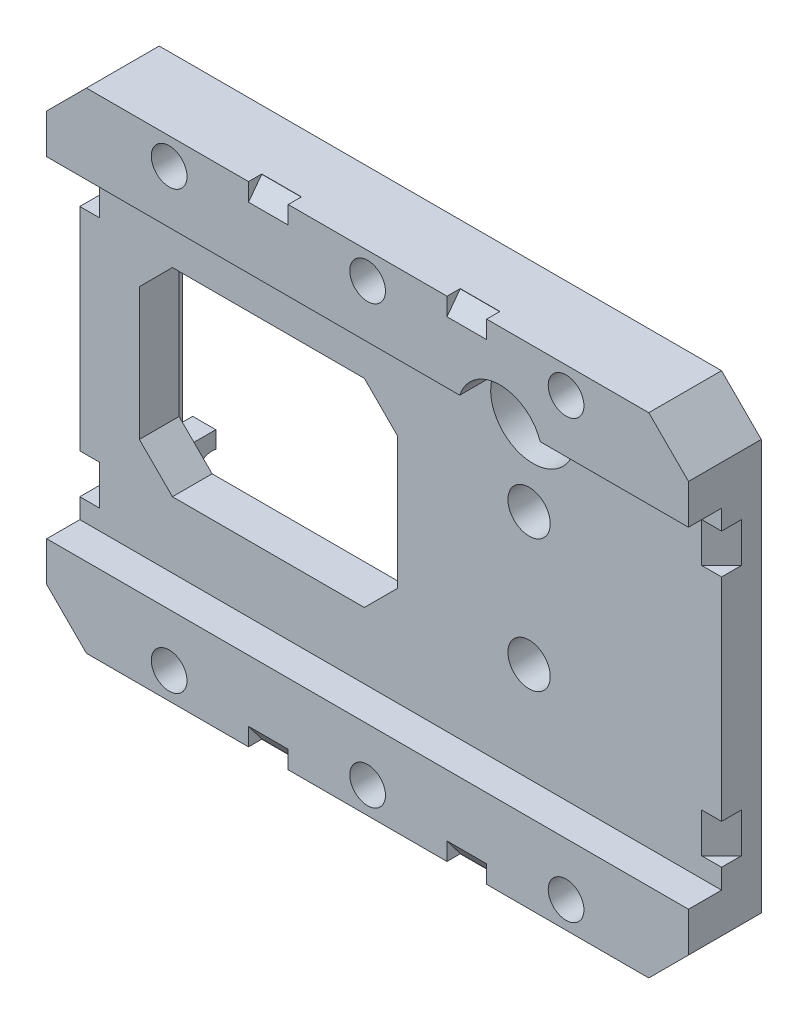
SolidWorks part; units mm, degrees
ref_plane "前视基准面" through (0, 0, 0) normal (0, 0, 1) x (1, 0, 0)
ref_plane "上视基准面" through (0, 0, 0) normal (0, 1, 0) x (1, 0, 0)
ref_plane "右视基准面" through (0, 0, 0) normal (1, 0, 0) x (0, 0, -1)
ref_plane "基准面4" through (0, 0, 5.028) normal (0, 0, -1) x (-1, 0, 0)
sketch "草图1" plane through (0, 0, 5.028) normal (0, 0, -1) x (-1, 0, 0)
  line L0 (-24.25, 18.5) -> (-24.25, -18.5)
  line L1 (-24.25, -18.5) -> (24.25, -18.5)
  line L2 (24.25, -18.5) -> (24.25, 18.5)
  line L3 (24.25, 18.5) -> (-24.25, 18.5)
  line L4 (-24.25, 0) -> (24.25, 0) construction
  line L5 (0, 18.5) -> (0, -18.5) construction
  point P8 (0, 0)
  dimension "D1" = 48.5
  dimension "D2" = 37
extrude "凸台-拉伸1" add sketch "草图1" against normal blind 7.5
sketch "草图2" plane through (24.25, 0, 0) normal (1, 0, 0) x (0, 0, -1)
  line L0 (-12.528, 12.5) -> (-12.528, -12.5)
  line L1 (-12.528, -12.5) -> (-8.028, -12.5)
  line L2 (-8.028, -12.5) -> (-8.028, 12.5)
  line L3 (-8.028, 12.5) -> (-12.528, 12.5)
extrude "切除-拉伸1" cut sketch "草图2" against normal through all
sketch "草图3" plane through (0, 0, 5.028) normal (0, 0, -1) x (-1, 0, 0)
  line L0 (21.75, 13.75) -> (21.75, -13.75)
  line L1 (21.75, -13.75) -> (-19.25, -13.75)
  line L2 (-19.25, -13.75) -> (-19.25, 13.75)
  line L3 (-19.25, 13.75) -> (21.75, 13.75)
  line L4 (-19.25, 0) -> (21.75, 0) construction
  line L5 (24.25, -18.5) -> (24.25, 18.5) construction
  line L6 (-24.25, 18.5) -> (-24.25, -18.5) construction
  point P4 (0, 0)
  point P8 (0, 0)
  point P9 (0, 0)
  dimension "D1" = 27.5
  dimension "D2" = 2.5
  dimension "D3" = 5
extrude "凸台-拉伸2" add sketch "草图3" along normal blind 3.028
sketch "草图4" plane through (0, 0, 2) normal (0, 0, -1) x (-1, 0, 0)
  line L0 (-18.25, -12.5) -> (20, -12.5)
  line L1 (20, -12.5) -> (20, 12.5)
  line L2 (20, 12.5) -> (-18.25, 12.5)
  line L3 (-18.25, 12.5) -> (-18.25, -12.5)
  line L5 (21.75, -13.75) -> (21.75, 13.75) construction
  line L6 (-19.25, 13.75) -> (-19.25, -13.75) construction
  line L7 (-19.25, -13.75) -> (21.75, -13.75) construction
  point P8 (0, 0)
  dimension "D1" = 1
  dimension "D2" = 1.25
  dimension "D3" = 1.75
extrude "切除-拉伸2" cut sketch "草图4" against normal blind 3.028
sketch "草图5" plane through (18.25, 0, 0) normal (-1, 0, 0) x (0, 0, 1)
  line L0 (2, 7.0344) -> (2, -7.0344)
  arc A0 (2, -7.0344) -> (2, 7.0344) centre (-7.722, 0) ccw
extrude "切除-拉伸3" cut sketch "草图5" against normal through all
sketch "草图6" plane through (-21.75, 0, 0) normal (-1, 0, 0) x (0, 0, 1)
  line L0 (2, 7.0344) -> (2, -7.0344)
  arc A0 (2, -7.0344) -> (2, 7.0344) centre (-7.722, 0) ccw
extrude "切除-拉伸4" cut sketch "草图6" against normal through all
sketch "草图7" plane through (0, 0, 8.028) normal (0, 0, 1) x (1, 0, 0)
  line L0 (-7.9784, 7.0292) -> (-13.0216, 7.0292)
  line L1 (-13.0216, -7.0292) -> (-7.9784, -7.0292)
  arc A0 (-1.5, 0) -> (-7.9784, 7.0292) centre (-7.9784, 0.5292) ccw
  arc A1 (-13.0216, 7.0292) -> (-19.5, 0) centre (-13.0216, 0.5292) ccw
  arc A2 (-19.5, 0) -> (-13.0216, -7.0292) centre (-13.0216, -0.5292) ccw
  arc A3 (-7.9784, -7.0292) -> (-1.5, 0) centre (-7.9784, -0.5292) ccw
  dimension "D1" = 19.5
  dimension "D2" = 18
extrude "切除-拉伸5" cut sketch "草图7" against normal through all
ref_plane "基准面5" through (0, 11.5, 0) normal (0, 1, 0) x (1, 0, 0)
sketch "草图8" plane through (0, 11.5, 0) normal (0, 1, 0) x (1, 0, 0)
  line L0 (13, -2.1) -> (10, -2.1)
  line L1 (10, -2.1) -> (10, -12.528)
  line L2 (10, -12.528) -> (13, -12.528)
  line L3 (13, -12.528) -> (13, -2.1)
  line L4 (10, -2.1) -> (10, -12.528) construction
hole_wizard "Ø2.5 (2.5) 直径孔1" positions "草图10" profile "草图9" hole size "Ø2.5" standard "ANSI Metric"
sketch "草图10" plane through (-21.75, 0, 0) normal (-1, 0, 0) x (0, 0, 1)
  point P0 (2.278, 10)
sketch "草图9" plane through (-21.75, 10, 2.278) normal (0, 1, 0) x (0, 0, 1)
  line L0 (0, 0) -> (0, 1.75)
  line L1 (0, 1.75) -> (1.25, 1.75)
  line L2 (1.25, 1.75) -> (1.25, 0)
  line L5 (1.25, 0) -> (0, 0)
  line L11 (0, -6.35) -> (0, 107.95) construction
  dimension "通孔孔直径" = 2.5
  dimension "通孔孔深度" = 1.75
hole_wizard "Ø2.5 (2.5) 直径孔2" positions "草图12" profile "草图11" hole size "Ø2.5" standard "ANSI Metric"
sketch "草图12" plane through (18.25, 0, 0) normal (-1, 0, 0) x (0, 0, 1)
  point P0 (2.278, -10)
  point P1 (2.278, 10)
sketch "草图11" plane through (18.25, -10, 2.278) normal (0, 1, 0) x (0, 0, 1)
  line L0 (0, 0) -> (0, 6)
  line L1 (0, 6) -> (1.25, 6)
  line L2 (1.25, 6) -> (1.25, 0)
  line L5 (1.25, 0) -> (0, 0)
  line L11 (0, -6.35) -> (0, 107.95) construction
  dimension "通孔孔直径" = 2.5
  dimension "通孔孔深度" = 6
hole_wizard "Ø2.5 (2.5) 直径孔3" positions "草图14" profile "草图13" hole size "Ø2.5" standard "ANSI Metric"
sketch "草图14" plane through (-20, 0, 0) normal (1, 0, 0) x (0, 0, -1)
  point P0 (-2.278, -10)
sketch "草图13" plane through (-20, -10, 2.278) normal (0, 1, 0) x (0, 0, -1)
  line L0 (0, 0) -> (0, 4.25)
  line L1 (0, 4.25) -> (1.25, 4.25)
  line L2 (1.25, 4.25) -> (1.25, 0)
  line L5 (1.25, 0) -> (0, 0)
  line L11 (0, -6.35) -> (0, 107.95) construction
  dimension "通孔孔直径" = 2.5
  dimension "通孔孔深度" = 4.25
hole_wizard "Ø2.7 (2.7) 直径孔1" positions "草图16" profile "草图15" hole size "Ø2.7" standard "ANSI Metric" end condition through all
sketch "草图16" plane through (0, 0, 12.528) normal (0, 0, 1) x (1, 0, 0)
  point P0 (0, -16.5)
  point P1 (-15, -16.5)
  point P2 (15, -16.5)
  point P3 (0, 16.5)
  point P4 (-15, 16.5)
  point P5 (15, 16.5)
sketch "草图15" plane through (0, -16.5, 12.528) normal (1, 0, 0) x (0, -1, 0)
  line L0 (0, 0) -> (0, 10.528)
  line L1 (0, 10.528) -> (1.35, 10.528)
  line L2 (1.35, 10.528) -> (1.35, 0)
  line L5 (1.35, 0) -> (0, 0)
  line L11 (0, -6.35) -> (0, 107.95) construction
  dimension "通孔孔直径" = 2.7
  dimension "通孔孔深度" = 10.528
chamfer "倒角1" distance 3 angle 45 4 edges at (24.25, -18.5, 8.778) (24.25, 18.5, 8.778) (-24.25, 18.5, 8.778) (-24.25, -18.5, 8.778)
sketch "草图17" plane through (0, 0, 12.528) normal (0, 0, 1) x (1, 0, 0)
  line L0 (-15, -16.5) -> (0, -16.5) construction
  line L1 (-9, -14.5) -> (-9, -18.5)
  line L2 (-9, -14.5) -> (-6, -14.5)
  line L3 (-9, -18.5) -> (-6, -18.5)
  line L4 (-6, -14.5) -> (-6, -18.5)
  line L5 (-9, -14.5) -> (-6, -18.5) construction
  line L6 (-9, -18.5) -> (-6, -14.5) construction
  line L7 (21.25, -18.5) -> (-21.25, -18.5) construction
  line L8 (0, -5.7904) -> (0, 5.7904) construction
  line L9 (9, -18.5) -> (6, -14.5) construction
  line L10 (9, -14.5) -> (6, -18.5) construction
  line L11 (6, -14.5) -> (6, -18.5)
  line L12 (9, -18.5) -> (6, -18.5)
  line L13 (9, -14.5) -> (6, -14.5)
  line L14 (9, -14.5) -> (9, -18.5)
  line L15 (5.7904, 0) -> (-5.7904, 0) construction
  line L16 (9, 14.5) -> (6, 18.5) construction
  line L17 (9, 18.5) -> (6, 14.5) construction
  line L18 (-9, 18.5) -> (-6, 14.5) construction
  line L19 (-9, 14.5) -> (-6, 18.5) construction
  line L20 (9, 14.5) -> (9, 18.5)
  line L21 (9, 14.5) -> (6, 14.5)
  line L22 (9, 18.5) -> (6, 18.5)
  line L23 (6, 14.5) -> (6, 18.5)
  line L24 (-6, 14.5) -> (-6, 18.5)
  line L25 (-9, 18.5) -> (-6, 18.5)
  line L26 (-9, 14.5) -> (-6, 14.5)
  line L27 (-9, 14.5) -> (-9, 18.5)
  point P4 (-7.5, -16.5)
  point P6 (-7.5, -16.5)
  point P18 (7.5, -16.5)
  point P29 (7.5, 16.5)
  point P30 (-7.5, 16.5)
  dimension "D1" = 3
extrude "切除-拉伸8" cut sketch "草图17" against normal blind 3
chamfer "倒角2" distance 3 angle 53 4 edges at (7.5, -14.5, 9.528) (-7.5, -14.5, 9.528) (-7.5, 14.5, 9.528) (7.5, 14.5, 9.528) first distance on face at (7.5, -14.5, 11.028) first distance on face at (-7.5, -14.5, 11.028) first distance on face at (-7.5, 14.5, 11.028) first distance on face at (7.5, 14.5, 11.028)
sketch "草图19" plane through (0, 0, 8.028) normal (0, 0, 1) x (1, 0, 0)
  line L0 (-24.25, -12.5) -> (-24.25, 12.5) construction
  line L1 (-24.25, -11) -> (-22.25, -11)
  line L2 (-24.25, -11) -> (-24.25, -8)
  line L3 (-24.25, -8) -> (-22.25, -8)
  line L4 (-22.25, -11) -> (-22.25, -8)
  line L6 (5.7904, 0) -> (-5.7904, 0) construction
  line L7 (-22.25, 11) -> (-22.25, 8)
  line L8 (-24.25, 8) -> (-22.25, 8)
  line L9 (-24.25, 11) -> (-24.25, 8)
  line L10 (-24.25, 11) -> (-22.25, 11)
  line L11 (-24.25, -14) -> (24.25, -14) construction
  line L12 (-24.25, -15.5) -> (-24.25, -12.5) construction
  line L13 (24.25, -12.5) -> (24.25, -15.5) construction
  line L14 (0, -14) -> (0, 21.3882) construction
  line L15 (24.25, 11) -> (22.25, 11)
  line L16 (24.25, 11) -> (24.25, 8)
  line L17 (24.25, 8) -> (22.25, 8)
  line L18 (22.25, 11) -> (22.25, 8)
  line L19 (22.25, -11) -> (22.25, -8)
  line L20 (24.25, -8) -> (22.25, -8)
  line L21 (24.25, -11) -> (24.25, -8)
  line L22 (24.25, -11) -> (22.25, -11)
  dimension "D1" = 3
  dimension "D2" = 2
  dimension "D3" = 8
extrude "切除-拉伸9" cut sketch "草图19" against normal blind 1.5
chamfer "倒角3" distance 2 angle 45 4 edges at (22.25, 9.5, 6.528) (22.25, -9.5, 6.528) (-22.25, 9.5, 6.528) (-22.25, -9.5, 6.528)
chamfer "倒角4" distance 1 angle 45 4 edges at (19.25, 13.75, 3.514) (19.25, -13.75, 3.514) (-21.75, -13.75, 3.514) (-21.75, 13.75, 3.514)
sketch "草图20" plane through (0, 0, 2) normal (0, 0, -1) x (-1, 0, 0)
  line L0 (-10, 11.5) -> (-13, 11.5) construction
  circle A0 centre (-10, 11.5) radius 3.2
extrude "切除-拉伸10" cut sketch "草图20" against normal blind 21.5
sketch "草图21" plane through (0, 0, 8.028) normal (0, 0, 1) x (1, 0, 0)
  line L1 (-19.75, -7.5) -> (-0.25, -7.5)
  line L2 (-19.75, -7.5) -> (-19.75, 7.5)
  line L3 (-19.75, 7.5) -> (-0.25, 7.5)
  line L4 (-0.25, -7.5) -> (-0.25, 7.5)
  line L5 (-19.75, -7.5) -> (-0.25, 7.5) construction
  line L6 (-19.75, 7.5) -> (-0.25, -7.5) construction
  point P0 (-10, 0)
  dimension "D1" = 10
  dimension "D2" = 19.5
  dimension "D3" = 15
extrude "切除-拉伸11" cut sketch "草图21" against normal blind 21.5
chamfer "倒角5" distance 2.5 angle 45 4 edges at (-0.25, -7.5, 6.528) (-0.25, 7.5, 6.528) (-19.75, -7.5, 6.528) (-19.75, 7.5, 6.528)
sketch "草图22" plane through (19.25, 0, 0) normal (1, 0, 0) x (0, 0, -1)
  line L1 (4.5, -7.5) -> (-4.5, -7.5)
  line L2 (4.5, -7.5) -> (4.5, 7.5)
  line L3 (4.5, 7.5) -> (-4.5, 7.5)
  line L4 (-4.5, -7.5) -> (-4.5, 7.5)
  line L5 (4.5, -7.5) -> (-4.5, 7.5) construction
  line L6 (4.5, 7.5) -> (-4.5, -7.5) construction
  point P0 (0, 0)
  dimension "D1" = 9
  dimension "D2" = 15
extrude "切除-拉伸12" cut sketch "草图22" against normal blind 51.5
sketch "草图23" plane through (0, -18.5, 0) normal (0, -1, 0) x (1, 0, 0)
  line L0 (24.25, 12.528) -> (24.25, 5.028) construction
  line L1 (-24.25, 12.528) -> (24.25, 12.528)
  line L2 (-24.25, 12.528) -> (-24.25, 10.528)
  line L3 (-24.25, 10.528) -> (24.25, 10.528)
  line L4 (24.25, 12.528) -> (24.25, 10.528)
  dimension "D1" = 2
extrude "切除-拉伸13" cut sketch "草图23" against normal blind 50
sketch "草图24" plane through (0, 0, 8.028) normal (0, 0, 1) x (1, 0, 0)
  line L0 (5.7904, 0) -> (-5.7904, 0) construction
  circle A0 centre (9.7038, 5) radius 1.6
  circle A1 centre (9.7038, -5) radius 1.6
  dimension "D1" = 10
  dimension "D2" = 3.2
extrude "切除-拉伸14" cut sketch "草图24" against normal blind 10
